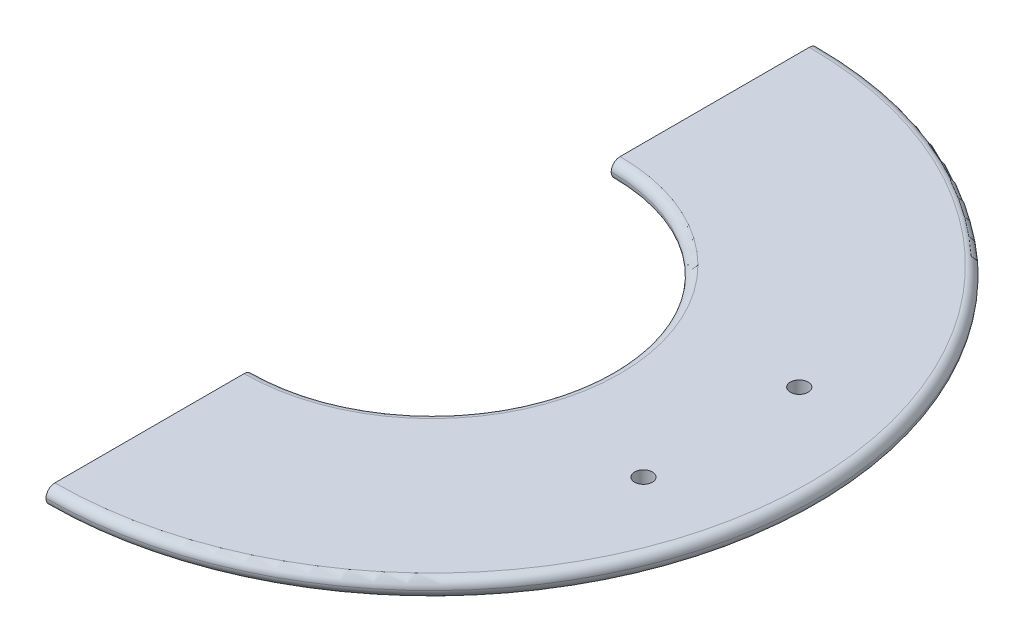
SolidWorks part; units mm, degrees
ref_plane "Front Plane" through (0, 0, 0) normal (0, 0, 1) x (1, 0, 0)
ref_plane "Top Plane" through (0, 0, 0) normal (0, 1, 0) x (1, 0, 0)
ref_plane "Right Plane" through (0, 0, 0) normal (1, 0, 0) x (0, 0, -1)
sketch "Sketch1" plane through (0, 0, 0) normal (0, 1, 0) x (1, 0, 0)
  line L0 (0, 86.75) -> (0, 40.25)
  line L1 (0, -40.25) -> (0, -86.75)
  arc A0 (0, 40.25) -> (0, -40.25) centre (0, 0) ccw
  arc A1 (0, 86.75) -> (0, -86.75) centre (0, 0) ccw
  dimension "D1" = 173.5
  dimension "D2" = 80.5
extrude "Boss-Extrude1" add sketch "Sketch1" along normal blind 4
sketch "Sketch2" plane through (0, 0, 0) normal (0, -1, 0) x (1, 0, 0)
  line L1 (-2.5, -83.75) -> (-14.5, -83.75)
  line L2 (-2.5, -83.75) -> (-2.5, -73.75)
  line L3 (-2.5, -73.75) -> (-14.5, -73.75)
  line L4 (-14.5, -83.75) -> (-14.5, -73.75)
  line L5 (0, -40.25) -> (0, -86.75) construction
  dimension "D1" = 12
  dimension "D2" = 10
  dimension "D3" = 3
  dimension "D4" = 2.5
extrude "Boss-Extrude2" add sketch "Sketch2" along normal blind 5
sketch "Sketch3" plane through (0, 0, -83.75) normal (0, 0, -1) x (-1, 0, 0)
  line L1 (2.5, -5) -> (14.5, -5)
  line L2 (2.5, -5) -> (2.5, -1.5)
  line L3 (2.5, -1.5) -> (14.5, -1.5)
  line L4 (14.5, -5) -> (14.5, -1.5)
  line L5 (14.5, -5) -> (14.5, 0) construction
  dimension "D1" = 3.5
extrude "Boss-Extrude3" add sketch "Sketch3" along normal blind 5
fillet "Fillet1" radius 1 9 edges at (-14.5, -5, -81.25) (-2.5, -5, -81.25) (-2.5, -1.5, -86.25) (-14.5, -1.5, -86.25) (-8.5, -5, -73.75) (-8.5, -5, -88.75) (-8.5, -1.5, -88.75) (-14.5, -3.25, -88.75) (-2.5, -3.25, -88.75)
fillet "Fillet2" radius 2 4 edges at (-86.75, 4, 0) (-40.25, 0, 0) (-86.75, 0, 0) (-40.25, 4, 0)
sketch "Sketch4" plane through (0, 4, 0) normal (0, 1, 0) x (1, 0, 0)
  line L0 (0, 0) -> (-65, 0) construction
  line L1 (-65, -17.5) -> (-65, 17.5) construction
  circle A0 centre (-65, -17.5) radius 2
  circle A1 centre (-65, 17.5) radius 2
  point P5 (-65, 0)
  dimension "D1" = 35
  dimension "D2" = 65
hole_wizard "Ø4.0mm Dowel Hole1" positions "3DSketch1" profile "Sketch5" hole size "Ø4.0" standard "ANSI Metric" end condition through all
sketch3d "3DSketch1"
  point P0 (-65, 4, 17.5)
  point P3 (-65, 4, -17.5)
sketch "Sketch5" plane through (-65, 4, 17.5) normal (1, 0, 0) x (0, 0, 1)
  line L0 (0, 0) -> (0, 9)
  line L1 (0, 9) -> (2, 9)
  line L2 (2, 9) -> (2, 0)
  line L5 (2, 0) -> (0, 0)
  line L11 (0, -6.35) -> (0, 107.95) construction
  dimension "Thru Hole Dia." = 4
  dimension "Thru Hole Depth" = 9
ref_plane "Plane1" through (0, 0, 0) normal (1, 0, 0) x (0, 0, -1)
mirror "Mirror1" about plane through (0, 0, 0) normal (1, 0, 0) of bodies 106
sketch "Sketch6" plane through (0, 0, 0) normal (1, 0, 0) x (0, 0, -1)
  line L1 (100.5733, 37.6973) -> (-96.1419, 37.6973)
  line L2 (100.5733, 37.6973) -> (100.5733, -33.7938)
  line L3 (100.5733, -33.7938) -> (-96.1419, -33.7938)
  line L4 (-96.1419, 37.6973) -> (-96.1419, -33.7938)
extrude "Cut-Extrude1" cut sketch "Sketch6" against normal up to next
